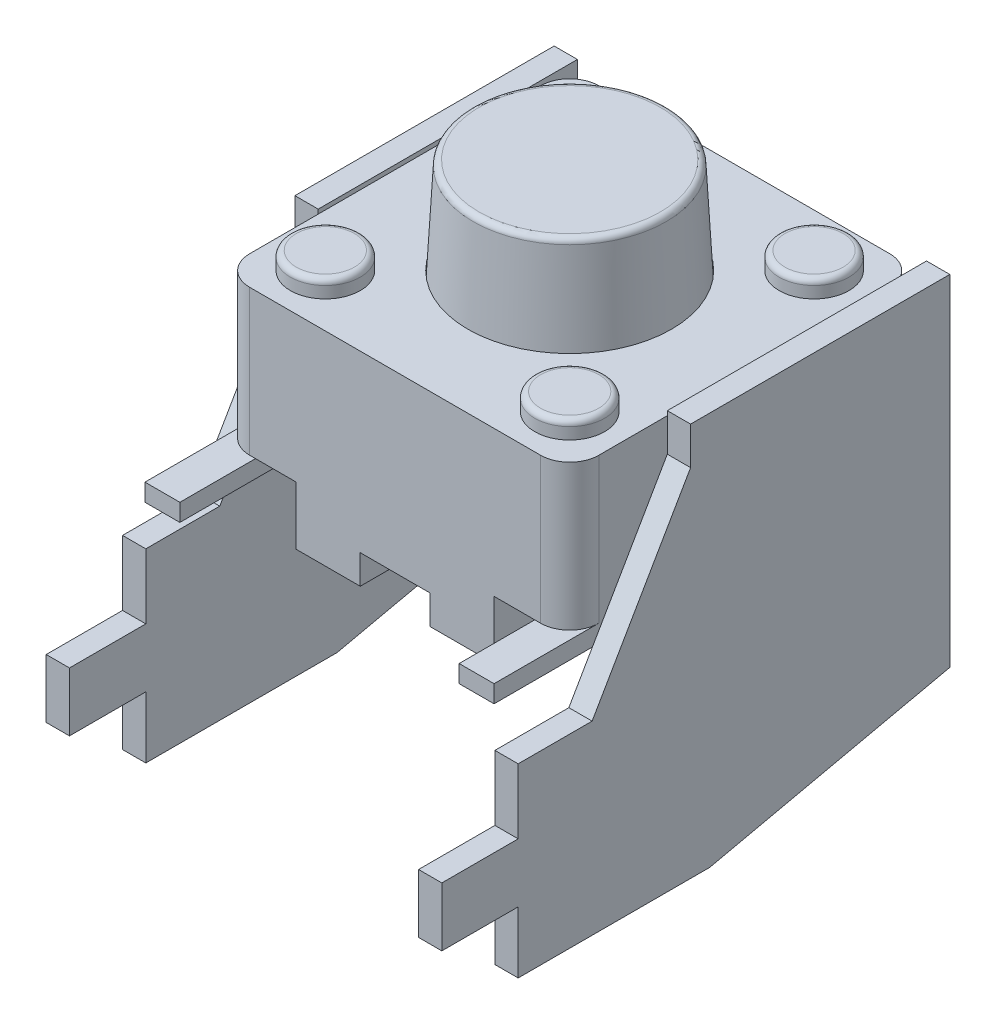
SolidWorks part; units mm, degrees
material "Custom Plastic"
ref_plane "Front Plane" through (0, 0, 0) normal (0, 0, 1) x (1, 0, 0)
ref_plane "Top Plane" through (0, 0, 0) normal (0, 1, 0) x (1, 0, 0)
ref_plane "Right Plane" through (0, 0, 0) normal (1, 0, 0) x (0, 0, -1)
sketch "Sketch1" plane through (0, 0, 0) normal (0, 1, 0) x (1, 0, 0)
  line L0 (-3.2652, 0) -> (3.207, 0) construction
  line L1 (-2.5, 3) -> (2.5, 3)
  line L2 (-3, 2.5) -> (-3, -2.5)
  line L3 (-2.5, -3) -> (2.5, -3)
  line L4 (3, 2.5) -> (3, -2.5)
  line L5 (-3, 3) -> (3, -3) construction
  line L6 (-3, -3) -> (3, 3) construction
  line L7 (0, -3.1905) -> (0, 3.2124) construction
  line L8 (3, 0) -> (2.4, 0)
  line L9 (3, 0) -> (3, -0.3)
  line L10 (3, -0.3) -> (2.4, -0.3)
  line L11 (2.4, 0) -> (2.4, -0.3)
  line L12 (-3, -0.3) -> (-2.4, -0.3)
  line L13 (-2.4, 0) -> (-2.4, -0.3)
  line L14 (-3, 0) -> (-2.4, 0)
  circle A0 centre (2.1, 2.1) radius 0.6
  circle A1 centre (2.1, -2.1) radius 0.6
  circle A2 centre (-2.1, -2.1) radius 0.6
  circle A3 centre (-2.1, 2.1) radius 0.6
  circle A4 centre (0, 0) radius 1.75
  arc A5 (2.5, 3) -> (3, 2.5) centre (2.5, 2.5) cw
  arc A6 (2.5, -3) -> (3, -2.5) centre (2.5, -2.5) ccw
  arc A7 (-3, -2.5) -> (-2.5, -3) centre (-2.5, -2.5) ccw
  arc A8 (-2.5, 3) -> (-3, 2.5) centre (-2.5, 2.5) ccw
  point P0 (0, 0)
  point P1 (0, 0)
  point P9 (0, 0)
  point P18 (0, 0)
  dimension "D1" = 6
  dimension "D2" = 0.9
  dimension "D3" = 1.2
  dimension "D5" = 3.5
  dimension "D6" = 0.5
  dimension "D7" = 0.6
  dimension "D8" = 0.3
  dimension "D4" = 4
extrude "Base" add sketch "Sketch1" along normal blind 3.3 contours L14 L2 L12 L13 | L1 A8 L2 L14 L13 L12 A7 L3 A6 L4 L10 L11 L8 A5 A0 A1 A2 A3 A4 | A3 | A2 | A4 | A1 | L8 L11 L10 L4 | A0 region at (0, 0, -2.9151) region at (-2.7, 0, 0.15) region at (2.7, 0, 0.15) region at (2.1, 0, -2.1) region at (2.1, 0, 2.1) region at (-2.1, 0, 2.1) region at (-2.1, 0, -2.1) region at (0, 0, 0)
extrude "Top Plate" add sketch "Sketch1<3>" along normal blind 0.2 from surface separate body contours L1 A8 L2 L14 L13 L12 A7 L3 A6 L4 L10 L11 L8 A5 A0 A1 A2 A3 A4 | L8 L11 L10 L4 | L14 L2 L12 L13 region at (0, 0, -2.9151) region at (-2.7, 0, 0.15) region at (2.7, 0, 0.15) starting at face at (0, 3.3, 0)
sketch "Sketch1<3>" plane through (0, 0, 0) normal (0, 1, 0) x (1, 0, 0) same geometry as "Sketch1"
extrude "Knobs" add sketch "Sketch1<4>" along normal blind 0.5 from offset 3.3 contours A1 | A2 | A3 | A0 region at (2.1, 0, -2.1) region at (2.1, 0, 2.1) region at (-2.1, 0, 2.1) region at (-2.1, 0, -2.1)
sketch "Sketch1<4>" plane through (0, 0, 0) normal (0, 1, 0) x (1, 0, 0) same geometry as "Sketch1"
extrude "Actuator" add sketch "Sketch1<5>" along normal blind 1.85 draft 3 from surface separate body contours A4 region at (0, 0, 0) starting at face at (-2.1, 3.3, -1.5)
sketch "Sketch1<5>" plane through (0, 0, 0) normal (0, 1, 0) x (1, 0, 0) same geometry as "Sketch1"
sketch "Sketch2" plane through (0, 0, 0) normal (0, -1, 0) x (1, 0, 0)
  line L0 (0, 3) -> (0.6, 3)
  line L1 (0, 3) -> (0, -3) construction
  line L2 (-2.5, 3) -> (2.5, 3) construction
  line L3 (0.6, 3) -> (1.7, 3)
  line L4 (0, -3) -> (0.6, -3)
  line L5 (-1.7, -2) -> (-3, -2)
  line L6 (0.6, -3) -> (0.6, 3)
  line L7 (-1.7, -0.9) -> (-1.7, -2)
  line L8 (-1.7, -0.9) -> (-3, -0.9)
  line L9 (1.7, -0.9) -> (3, -0.9)
  line L10 (1.7, -0.9) -> (1.7, -2)
  line L11 (-3, -0.4) -> (-1.7, -0.4)
  line L12 (-0.6, -3) -> (-0.6, 3)
  line L13 (1.7, 3) -> (1.7, -0.4)
  line L14 (-1.7, 3) -> (-1.7, -0.4)
  line L15 (3, 0) -> (-3, 0) construction
  line L16 (-3, -2.5) -> (-3, 2.5) construction
  line L21 (-2.5, -3) -> (2.5, -3) construction
  line L22 (1.7, -2) -> (3, -2)
  line L23 (3, -2.5) -> (3, 2.5) construction
  line L25 (3, -0.4) -> (1.7, -0.4)
  point P5 (0, 0)
  point P12 (0, 0)
  arc M1 (3, 2.5) -> (2.5, 3) centre (2.5, 2.5) ccw
  line M2 (2.5, 3) -> (-2.5, 3)
  arc M3 (-2.5, 3) -> (-3, 2.5) centre (-2.5, 2.5) ccw
  line M4 (-3, 2.5) -> (-3, -2.5)
  line M6 (-2.5, -3) -> (2.5, -3)
  line M8 (3, -2.5) -> (3, 2.5)
  dimension "D1" = 0.6
  dimension "D2" = 1.7
  dimension "D3" = 0.4
  dimension "D4" = 1
  dimension "D6" = 0.5
extrude "Base Leg Cutout" cut sketch "Sketch2" against normal blind 1 from surface contours L14 L11 M2 M3 M4 | L25 L13 M8 M1 M2 region at (2.3434, 0, 1.2805) region at (-2.3434, 0, 1.2805) starting at face at (0, 0, 0)
extrude "Base Shallow Cutout" cut sketch "Sketch2<3>" against normal blind 0.5 contours L1 L12 M2 M6 | L10 L22 L9 M8 | L7 L8 L5 M4 region at (2.35, 0, -1.45) region at (-2.35, 0, -1.45) region at (0, 0, 0)
sketch "Sketch2<3>" plane through (0, 0, 0) normal (0, -1, 0) x (1, 0, 0) same geometry as "Sketch2"
extrude "Pins" add sketch "Sketch1<7>" against normal blind 0.3 from offset 1 separate body contours L14 L2 L12 L13 | L8 L11 L10 L4 region at (-2.7, 0, 0.15) region at (2.7, 0, 0.15)
sketch "Sketch1<7>" plane through (0, 0, 0) normal (0, 1, 0) x (1, 0, 0) same geometry as "Sketch1"
fillet "Fillet1" radius 0.1 1 edges at (0, 5.15, 1.653)
fillet "Fillet2" radius 0.1 4 edges at (-2.1, 3.8, -1.5) (2.1, 3.8, -1.5) (-2.1, 3.8, 2.7) (2.1, 3.8, 2.7)
sketch "Sketch4" plane through (0, 0, 0.3) normal (0, 0, 1) x (1, 0, 0)
  line L4 (3, 1) -> (2.4, 1)
  line L5 (2.4, 1) -> (2.4, 0.7)
  line L6 (2.4, 0.7) -> (3, 0.7)
  line L7 (3, 0.7) -> (3, 1)
  line L8 (3, 1) -> (2.4, 1)
  line L9 (2.4, 1) -> (2.4, 0.7)
  line L10 (2.4, 0.7) -> (3, 0.7)
  line L11 (3, 0.7) -> (3, 1)
  line L12 (-2.4, 1) -> (-3, 1)
  line L13 (-3, 1) -> (-3, 0.7)
  line L14 (-3, 0.7) -> (-2.4, 0.7)
  line L15 (-2.4, 0.7) -> (-2.4, 1)
  line L16 (-2.4, 1) -> (-3, 1)
  line L17 (-3, 1) -> (-3, 0.7)
  line L18 (-3, 0.7) -> (-2.4, 0.7)
  line L19 (-2.4, 0.7) -> (-2.4, 1)
  dimension "D1" = 0
  dimension "D2" = 0
extrude "Boss-Extrude1" add sketch "Sketch4" along normal blind 4
sketch "Sketch6" plane through (3, 0, 0) normal (1, 0, 0) x (0, 0, -1)
  line L0 (3.1328, 3.575) -> (3.1328, -2.2739)
  line L1 (3.1328, -2.2739) -> (-0.9947, -3.1881)
  line L2 (-0.9947, -3.1881) -> (-4.2856, -3.1881)
  line L3 (-4.2856, -3.1881) -> (-4.2856, -2.1289)
  line L4 (-4.2856, -2.1289) -> (-7.4624, -2.1289)
  line L5 (-1.3225, 3.575) -> (-1.3225, 2.9268)
  line L6 (-7.4624, -1.117) -> (-4.2856, -1.117)
  line L7 (-4.2856, -1.117) -> (-4.2856, 0)
  line L8 (-4.2856, 0) -> (-3.0145, 0)
  line L10 (-1.3225, 3.575) -> (3.1328, 3.575)
  line L11 (-1.3225, 2.9268) -> (-3.0145, 0)
  arc A0 (-7.4624, -1.117) -> (-7.4624, -2.1289) centre (-7.4624, -1.6229) ccw
extrude "Boss-Extrude2" add sketch "Sketch6" along normal blind 0.4
sketch "Sketch7" plane through (-3, 0, 0) normal (-1, 0, 0) x (0, 0, 1)
  line L11 (1.3225, 3.575) -> (-3.1328, 3.575)
  line L12 (1.3225, 2.9268) -> (1.3225, 3.575)
  line L13 (3.0145, 0) -> (1.3225, 2.9268)
  line L14 (4.2856, 0) -> (3.0145, 0)
  line L15 (4.2856, -1.117) -> (4.2856, 0)
  line L16 (7.4624, -1.117) -> (4.2856, -1.117)
  line L17 (4.2856, -2.1289) -> (7.4624, -2.1289)
  line L18 (4.2856, -3.1881) -> (4.2856, -2.1289)
  line L19 (0.9947, -3.1881) -> (4.2856, -3.1881)
  line L20 (-3.1328, -2.2739) -> (0.9947, -3.1881)
  line L21 (-3.1328, 3.575) -> (-3.1328, -2.2739)
  line L22 (1.3225, 3.575) -> (-3.1328, 3.575)
  line L23 (1.3225, 2.9268) -> (1.3225, 3.575)
  line L24 (3.0145, 0) -> (1.3225, 2.9268)
  line L25 (4.2856, 0) -> (3.0145, 0)
  line L26 (4.2856, -1.117) -> (4.2856, 0)
  line L27 (7.4624, -1.117) -> (4.2856, -1.117)
  line L28 (4.2856, -2.1289) -> (7.4624, -2.1289)
  line L29 (4.2856, -3.1881) -> (4.2856, -2.1289)
  line L30 (0.9947, -3.1881) -> (4.2856, -3.1881)
  line L31 (-3.1328, -2.2739) -> (0.9947, -3.1881)
  line L32 (-3.1328, 3.575) -> (-3.1328, -2.2739)
  arc A1 (7.4624, -2.1289) -> (7.4624, -1.117) centre (7.4624, -1.6229) ccw
  arc A2 (7.4624, -2.1289) -> (7.4624, -1.117) centre (7.4624, -1.6229) ccw
  dimension "D1" = 0
extrude "Boss-Extrude3" add sketch "Sketch7" along normal blind 0.4
sketch "Sketch8" plane through (3.4, 0, 0) normal (1, 0, 0) x (0, 0, -1)
  line L0 (-4.2856, -1.117) -> (-7.4624, -1.117) construction
  line L1 (-5.5974, -1.117) -> (-7.9684, -1.117)
  line L2 (-5.5974, -1.117) -> (-5.5974, -2.1289)
  line L3 (-5.5974, -2.1289) -> (-7.9684, -2.1289)
  line L4 (-7.9684, -1.117) -> (-7.9684, -2.1289)
  line L5 (-7.4624, -2.1289) -> (-4.2856, -2.1289) construction
  arc A0 (-7.4624, -1.117) -> (-7.4624, -2.1289) centre (-7.4624, -1.6229) ccw construction
  dimension "D1" = 2.371
extrude "Cut-Extrude1" cut sketch "Sketch8" against normal through all both and the other way through all
